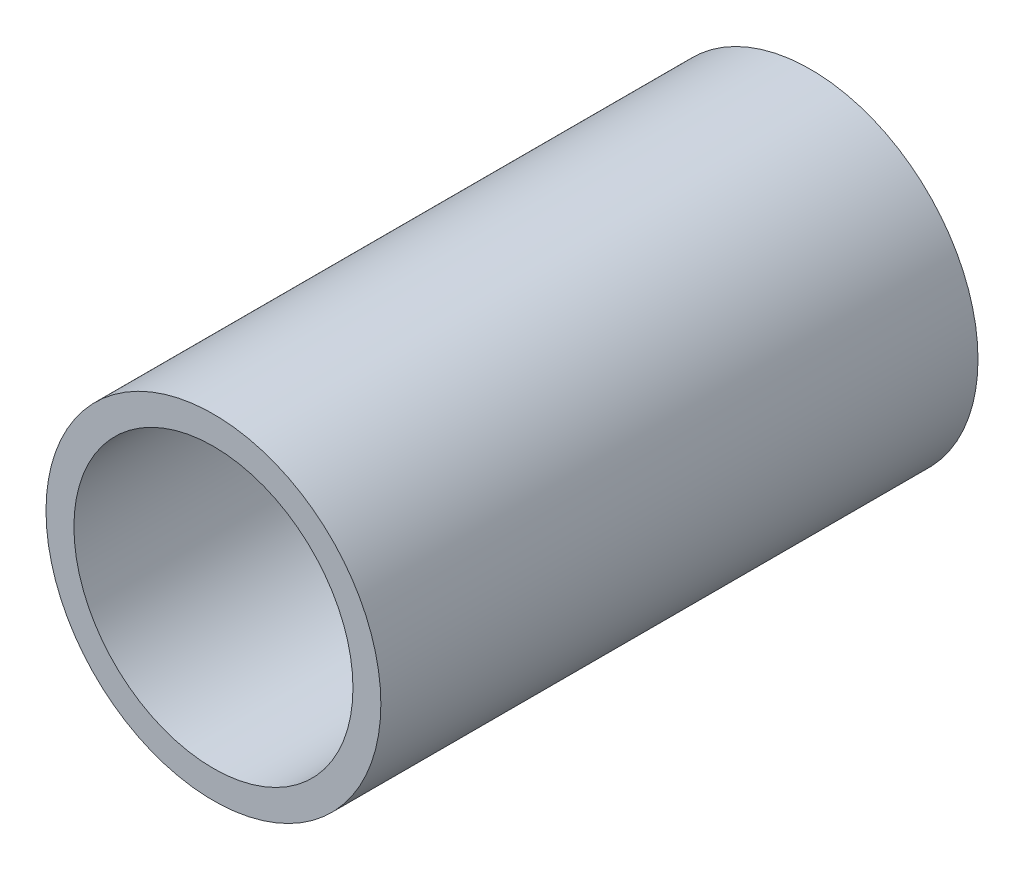
SolidWorks part; units mm, degrees
material "PLA 50%"
ref_plane "Front Plane" through (0, 0, 0) normal (0, 0, 1) x (1, 0, 0)
ref_plane "Top Plane" through (0, 0, 0) normal (0, 1, 0) x (1, 0, 0)
ref_plane "Right Plane" through (0, 0, 0) normal (1, 0, 0) x (0, 0, -1)
ref_axis "X" through (-88.99, 0, 0) along (1, 0, 0)
ref_axis "Y" through (0, 55, 0) along (0, -1, 0)
ref_axis "Z" through (0, 0, -88.99) along (0, 0, 1)
sketch "Sketch1" plane through (0, 0, 0) normal (0, 0, 1) x (1, 0, 0)
  circle A0 centre (0, 0) radius 5
  circle A1 centre (0, 0) radius 6
  dimension "D1" = 10
  dimension "D2" = 12
extrude "Boss-Extrude1" add sketch "Sketch1" against normal up to surface (21.3988 mm away)
